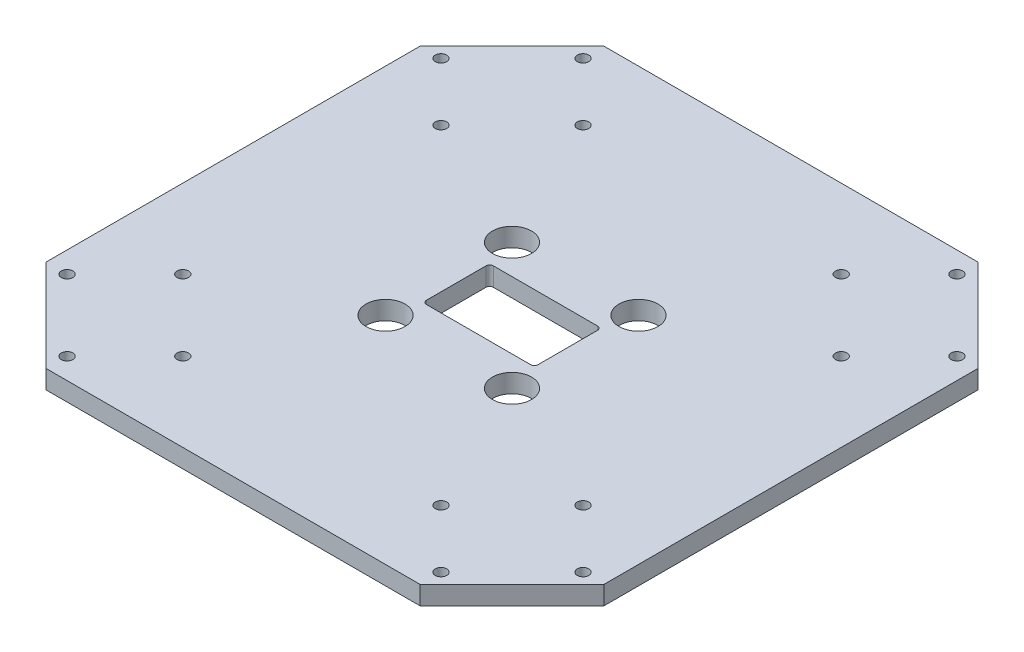
SolidWorks part; units mm, degrees
ref_plane "Front Plane" through (0, 0, 0) normal (0, 0, 1) x (1, 0, 0)
ref_plane "Top Plane" through (0, 0, 0) normal (0, 1, 0) x (1, 0, 0)
ref_plane "Right Plane" through (0, 0, 0) normal (1, 0, 0) x (0, 0, -1)
sketch "Sketch1" plane through (0, 0, 0) normal (0, 1, 0) x (1, 0, 0)
  line L1 (-75, 75) -> (75, 75)
  line L2 (-75, 75) -> (-75, -75)
  line L3 (-75, -75) -> (75, -75)
  line L4 (75, 75) -> (75, -75)
  line L5 (-75, 75) -> (75, -75) construction
  line L6 (-75, -75) -> (75, 75) construction
  point P0 (0, 0)
  dimension "D1" = 150
extrude "Boss-Extrude1" add sketch "Sketch1" along normal mid plane 5
sketch "Sketch2" plane through (0, 2.5, 0) normal (0, 1, 0) x (1, 0, 0)
  line L0 (50.2513, 75) -> (75, 75)
  line L1 (-15, 15) -> (15, 15)
  line L2 (-15, 15) -> (-15, -15)
  line L3 (-15, -15) -> (15, -15)
  line L4 (15, 15) -> (15, -15)
  line L5 (-15, 15) -> (15, -15) construction
  line L6 (-15, -15) -> (15, 15) construction
  line L7 (75, 75) -> (-75, 75) construction
  line L8 (75, -75) -> (75, 75) construction
  line L9 (75, 75) -> (75, 50.2513)
  line L10 (75, 50.2513) -> (50.2513, 75)
  line L11 (0, 0) -> (-24.6603, 0) construction
  line L12 (0, 0) -> (0, -37.7235) construction
  line L13 (-75, 75) -> (-75, 50.2513)
  line L14 (-50.2513, 75) -> (-75, 75)
  line L15 (-75, 50.2513) -> (-50.2513, 75)
  line L16 (-50.2513, -75) -> (-75, -75)
  line L17 (-75, -50.2513) -> (-50.2513, -75)
  line L18 (-75, -75) -> (-75, -50.2513)
  line L19 (75, -75) -> (75, -50.2513)
  line L20 (50.2513, -75) -> (75, -75)
  line L21 (75, -50.2513) -> (50.2513, -75)
  point P0 (0, 0)
  dimension "D1" = 30
  dimension "D2" = 35
extrude "Cut-Extrude1" cut sketch "Sketch2" against normal up to surface (5 mm away) contours L10 L0 L9 | L13 L15 L14 | L19 L21 L20 | L16 L18 L17 up to face at (0, -2.5, 0)
sketch "Sketch3" plane through (0, 2.5, 0) normal (0, 1, 0) x (1, 0, 0)
  line L0 (75, 50.2513) -> (50.2513, 75) construction
  line L1 (10, 10) -> (-10, 10)
  line L2 (10, 10) -> (10, -10)
  line L3 (10, -10) -> (-10, -10)
  line L4 (-10, 10) -> (-10, -10)
  line L5 (10, 10) -> (-10, -10) construction
  line L6 (10, -10) -> (-10, 10) construction
  line L7 (0, 0) -> (0, -7.7356) construction
  line L8 (0, 0) -> (-6.2026, 0) construction
  circle A2 centre (69.3431, 50.2513) radius 1.55
  circle A3 centre (53.7868, 34.6949) radius 1.55
  circle A5 centre (34.6949, 53.7868) radius 1.55
  circle A6 centre (50.2513, 69.3431) radius 1.55
  circle A7 centre (-69.3431, 50.2513) radius 1.55
  circle A8 centre (-53.7868, 34.6949) radius 1.55
  circle A11 centre (-34.6949, 53.7868) radius 1.55
  circle A12 centre (-50.2513, 69.3431) radius 1.55
  circle A13 centre (-53.7868, -34.6949) radius 1.55
  circle A14 centre (-69.3431, -50.2513) radius 1.55
  circle A17 centre (-34.6949, -53.7868) radius 1.55
  circle A18 centre (-50.2513, -69.3431) radius 1.55
  circle A19 centre (69.3431, -50.2513) radius 1.55
  circle A20 centre (53.7868, -34.6949) radius 1.55
  circle A23 centre (34.6949, -53.7868) radius 1.55
  circle A24 centre (50.2513, -69.3431) radius 1.55
  point P0 (0, 0)
  dimension "D2" = 3.1
  dimension "D4" = 13.5
  dimension "D6" = 22
  dimension "D8" = 4
  dimension "D3" = 13.5
  dimension "D1" = 20
extrude "Cut-Extrude2" cut sketch "Sketch3" against normal up to surface (5 mm away) contours A12 | A11 | A7 | A8 | A13 | A14 | A17 | A18 | A19 | A20 | A23 | A24 | A2 | A3 | A5 | A6 region at (69.3431, 2.5, -50.2513) region at (53.7868, 2.5, -34.6949) region at (34.6949, 2.5, -53.7868) region at (50.2513, 2.5, -69.3431) region at (-69.3431, 2.5, -50.2513) region at (-53.7868, 2.5, -34.6949) region at (-34.6949, 2.5, -53.7868) region at (-50.2513, 2.5, -69.3431) region at (-53.7868, 2.5, 34.6949) region at (-69.3431, 2.5, 50.2513) region at (-34.6949, 2.5, 53.7868) region at (-50.2513, 2.5, 69.3431) region at (69.3431, 2.5, 50.2513) region at (53.7868, 2.5, 34.6949) region at (34.6949, 2.5, 53.7868) region at (50.2513, 2.5, 69.3431) up to face at (0, -2.5, 0)
sketch "Sketch4" plane through (0, 2.5, 0) normal (0, 1, 0) x (1, 0, 0)
  line L0 (0, 0) -> (0, -6.9471) construction
  line L1 (15, 9) -> (-15, 9)
  line L2 (15, 9) -> (15, -9)
  line L3 (15, -9) -> (-15, -9)
  line L4 (-15, 9) -> (-15, -9)
  line L5 (15, 9) -> (-15, -9) construction
  line L6 (15, -9) -> (-15, 9) construction
  line L7 (0, 0) -> (-7.8354, 0) construction
  circle A0 centre (17, -17) radius 5.25
  circle A1 centre (17, 17) radius 5.25
  circle A2 centre (-17, -17) radius 5.25
  circle A3 centre (-17, 17) radius 5.25
  point P0 (0, 0)
  dimension "D3" = 10.5
  dimension "D5" = 17
  dimension "D1" = 18
  dimension "D2" = 30
  dimension "D4" = 17
extrude "Cut-Extrude3" cut sketch "Sketch4" against normal up to surface (5 mm away) up to face at (-34.6949, -2.5, -52.2368)
fillet "Fillet1" radius 1 4 edges at (-15, 0, 9) (-15, 0, -9) (15, 0, 9) (15, 0, -9)
